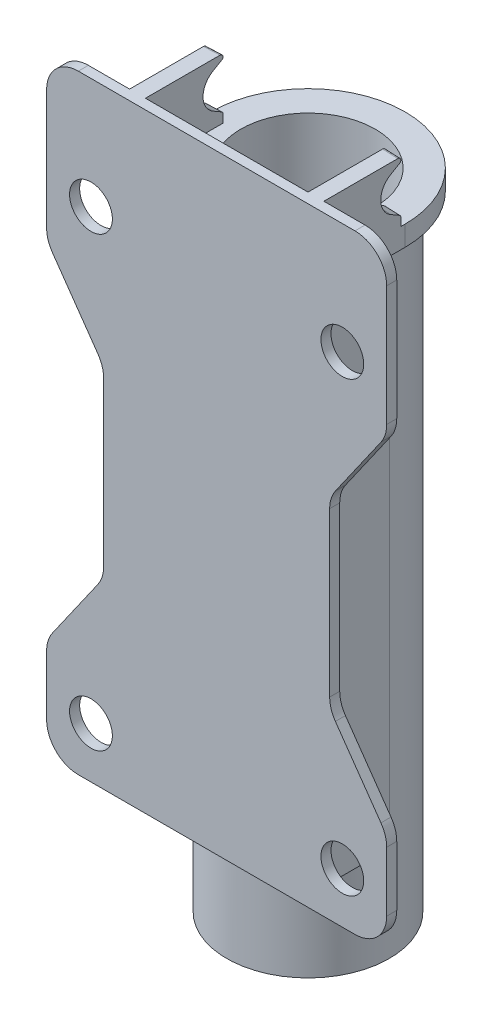
SolidWorks part; units mm, degrees
note: The reader was unsure of these and kept them because the rebuilt part matched: shared geometry of "Sketch33<3>".
other "pipe" parameters "D1"=877.6559, "D2"=75.5022, "D3"=726.6514, "D4"=726.6514, "D5"=877.6559, "D6"=4.445, "D7"=9.9955, "\"bearing_bore_min\""=42.164, "D8"=59.5421, "D9"=6.35, "D10"=1.4503
material "6061 Alloy"
ref_plane "Front Plane" through (0, 0, 0) normal (0, 0, 1) x (1, 0, 0)
ref_plane "Top Plane" through (0, 0, 0) normal (0, 1, 0) x (1, 0, 0)
ref_plane "Right Plane" through (0, 0, 0) normal (1, 0, 0) x (0, 0, -1)
sketch "Sketch11" plane through (0, 0, 0) normal (0, 0, 1) x (1, 0, 0)
  line L0 (0, 0) -> (0, 109.6398) construction
  line L1 (0, 0) -> (-89.1372, 0) construction
sketch "Sketch12" plane through (0, 0, 0) normal (0, 0, 1) x (1, 0, 0)
  line L0 (-25.65, 0) -> (-25.65, 203.2)
  line L1 (200000, 0) -> (-200089.1372, 0) construction
  line L4 (-21.2287, 0) -> (-25.65, 0)
  line L5 (-21.2287, 0) -> (-21.2287, 38.5)
  line L6 (-21.2287, 38.5) -> (-19.177, 38.5)
  line L7 (-19.177, 38.5) -> (-19.177, 164.7)
  line L8 (-19.177, 164.7) -> (-21.2287, 164.7)
  line L9 (-21.2287, 164.7) -> (-21.2287, 203.2)
  line L10 (-21.2287, 203.2) -> (-25.65, 203.2)
  line L13 (-21.2287, 203.2) -> (0, 203.2) construction
  line L14 (0, 203.2) -> (0, 0) construction
  line L15 (0, 0) -> (-21.2287, 0) construction
  point P12 (-25.4, 0)
  dimension "D4" = 38.5
  dimension "D5" = 203.2
  dimension "D6" = 4.4213
  dimension "D1" = 51.3
  dimension "D2" = 42.4573
  dimension "D8" = 50.8
  dimension "D9" = 0.25
  dimension "D3" = 38.354
  dimension "D7" = 2.0517
revolve "Revolve1" add sketch "Sketch12" angle 360 about L0
ref_plane "mideplane" through (0, 101.6, 0) normal (0, -1, 0) x (-1, 0, 0)
ref_plane "top pipe plane" through (0, 30, 0) normal (0, -1, 0) x (-1, 0, 0)
ref_plane "bottom pipe plane" through (0, 203.2, 0) normal (0, 1, 0) x (1, 0, 0)
ref_plane "pipe support midplane" through (0, 116.6, 0) normal (0, -1, 0) x (-1, 0, 0)
sketch "Sketch14" plane through (0, 30, 0) normal (0, -1, 0) x (-1, 0, 0)
  line L0 (0, 0) -> (-25.65, 0) construction
  line L1 (0, 0) -> (25.65, 0) construction
  line L7 (-25.65, -25.65) -> (25.65, -25.65)
  line L9 (25.65, -25.65) -> (25.65, 0)
  line L10 (-25.65, -25.65) -> (-25.65, 0)
  circle A0 centre (0, 0) radius 25.65 construction
  circle A1 centre (0, 0) radius 25.65
  circle A2 centre (0, 0) radius 25.65 construction
  arc A3 (25.65, 0) -> (-25.65, 0) centre (0, 0) cw
  dimension "D1" = 0
  dimension "D2" = 0
extrude "Boss-Extrude1" add sketch "Sketch14" against normal up to surface (173.2 mm away) contours A1 L10 L7 L9 | A1 L7 L9 up to plane "bottom pipe plane"
sketch "Sketch27" plane through (0, 0, 25.65) normal (0, 0, 1) x (1, 0, 0)
  line L0 (25.65, 30) -> (53.65, 30)
  line L1 (53.65, 30) -> (53.65, 62)
  line L2 (53.65, 62) -> (35.65, 87.7067)
  line L3 (35.65, 87.7067) -> (35.65, 145.4933)
  line L4 (35.65, 145.4933) -> (53.65, 171.2)
  line L5 (25.65, 30) -> (25.65, 203.2)
  line L6 (25.65, 203.2) -> (-25.65, 203.2)
  line L7 (-25.65, 203.2) -> (-25.65, 30)
  line L8 (-25.65, 30) -> (0, 30)
  line L9 (0, 30) -> (25.65, 30)
  line L10 (25.65, 30) -> (25.65, 203.2) construction
  line L11 (25.65, 203.2) -> (-25.65, 203.2)
  line L12 (-25.65, 203.2) -> (-25.65, 30)
  line L13 (-25.65, 30) -> (0, 30)
  line L14 (0, 30) -> (25.65, 30)
  line L15 (53.65, 171.2) -> (53.65, 203.2)
  line L16 (25.65, 203.2) -> (53.65, 203.2)
  line L17 (53.65, 62) -> (25.65, 62) construction
  line L18 (25.65, 62) -> (53.65, 30) construction
  line L19 (53.65, 171.2) -> (25.65, 171.2) construction
  line L20 (25.65, 171.2) -> (53.65, 203.2) construction
  line L24 (53.65, 203.2) -> (53.65, 222.25)
  line L25 (53.65, 222.25) -> (-25.65, 222.25)
  line L26 (-25.65, 222.25) -> (-25.65, 203.2)
  circle A0 centre (39.65, 46) radius 6 construction
  point P14 (39.65, 187.2)
  dimension "D2" = 12
  dimension "D3" = 10
  dimension "D6" = 8
  dimension "D4" = 10
  dimension "D5" = 55
  dimension "D7" = 19.05
  dimension "D1" = 0
extrude "Boss-Extrude2" add sketch "Sketch27" along normal blind 3.175
hole_wizard "M12 Clearance Hole1" positions "Sketch28" profile "Sketch29" hole size "M12" standard "ISO" end condition through all
sketch "Sketch28" plane through (0, 0, 25.65) normal (0, 0, -1) x (-1, 0, 0)
  point P0 (-39.65, 46)
  point P3 (-39.65, 187.2)
sketch "Sketch29" plane through (39.65, 46, 25.65) normal (1, 0, 0) x (0, 1, 0)
  line L0 (0, 0) -> (0, 3.175)
  line L1 (0, 3.175) -> (6.75, 3.175)
  line L2 (6.75, 3.175) -> (6.75, 0)
  line L5 (6.75, 0) -> (0, 0)
  line L11 (0, -6.35) -> (0, 107.95) construction
  dimension "Thru Hole Dia." = 13.5
  dimension "Thru Hole Depth" = 3.175
fillet "Fillet1" radius 10 6 edges at (53.65, 171.2, 27.2375) (35.65, 145.4933, 27.2375) (35.65, 87.7067, 27.2375) (53.65, 62, 27.2375) (53.65, 30, 27.2375) (53.65, 222.25, 27.2375)
mirror "Mirror1" about plane through (0, 0, 0) normal (1, 0, 0) of "Fillet1", "M12 Clearance Hole1", "Boss-Extrude2"
chamfer "Chamfer1" [suppressed] distance 1 angle 45
chamfer "Chamfer3" [suppressed] distance 1.85 angle 45
ref_plane "Plane6" through (0, 0, 25.65) normal (0, 0, -1) x (-1, 0, 0)
ref_plane "Plane4" through (0, 203.2, 0) normal (0, 1, 0) x (1, 0, 0)
sketch "Sketch25" plane through (0, 203.2, 0) normal (0, 1, 0) x (1, 0, 0)
  line L0 (-0.277, -6.344) -> (24.5509, -7.428) construction
  line L1 (0.277, 6.344) -> (25.1049, 5.2599) construction
  line L2 (0, 0) -> (25.6256, -1.1188) construction
  line L3 (0, 0) -> (25.6256, -1.1188) construction
  line L4 (35.6186, 0) -> (47.6837, 0) construction
  line L5 (24.5509, -7.428) -> (25.1049, 5.2599) construction
  circle A2 centre (0, 0) radius 25.65 construction
  circle A4 centre (0, 0) radius 6.35 construction
  arc A5 (25.65, 0) -> (-25.65, 0) centre (0, 0) ccw construction
  arc A6 (25.6256, -1.1188) -> (-25.65, 0) centre (0, 0) ccw
  circle A7 centre (0, 0) radius 25.4 construction
  dimension "D3" = 12.7
  dimension "D1" = 50.8
  dimension "D2" = 2.5
ref_plane "Plane5" through (24.8279, 0, 1.084) normal (0.999, 0, 0.0436) x (0.0436, 0, -0.999)
sketch "Sketch26" plane through (24.8279, 0, 1.084) normal (0.999, 0, 0.0436) x (0.0436, 0, -0.999)
  line L0 (-6.35, 203.2) -> (6.35, 203.2) construction
  line L1 (-6.35, 203.2) -> (6.35, 203.2) construction
  line L2 (-6.35, 203.2) -> (-6.35, 226.9306) construction
  circle A0 centre (0, 213.55) radius 6.35
  dimension "D1" = 12.7
  dimension "D2" = 4
sketch "Sketch33" plane through (0, 203.2, 0) normal (0, 1, 0) x (1, 0, 0)
  line L0 (30.65, -25.65) -> (30.65, 0)
  line L1 (-30.65, 0) -> (-30.65, -25.65)
  line L2 (-30.65, -25.65) -> (-25.65, -25.65)
  line L3 (-25.65, 0) -> (-25.65, -25.65)
  line L4 (-25.65, -25.65) -> (25.65, -25.65)
  line L5 (25.65, -25.65) -> (25.65, 0)
  line L6 (-25.65, 0) -> (-25.65, -25.65)
  line L7 (-25.65, -25.65) -> (25.65, -25.65)
  line L8 (25.65, -25.65) -> (25.65, 0)
  line L9 (25.65, -25.65) -> (30.65, -25.65)
  line L10 (0, 0) -> (25.6256, -1.1188) construction
  line L11 (0, 0) -> (25.6256, -1.1188) construction
  line L12 (25.6256, -1.1188) -> (30.65, -1.3382)
  arc A0 (30.65, 0) -> (-30.65, 0) centre (0, 0) ccw
  arc A1 (25.65, 0) -> (-25.65, 0) centre (0, 0) ccw
  arc A2 (25.65, 0) -> (-25.65, 0) centre (0, 0) ccw
  point P12 (30.65, -1.3382)
  arc M5 (25.65, 0) -> (-25.65, 0) centre (0, 0) ccw
  line M6 (-25.65, 0) -> (-25.65, -25.65)
  line M8 (25.65, -25.65) -> (25.65, 0)
  dimension "D1" = 0
  dimension "D2" = 5
extrude "Boss-Extrude3" add sketch "Sketch33" against normal blind 6.35 contours L0 A0 L1 L2 L9 M6 M5 M8 | L12 L9 L0 M8
extrude "Boss-Extrude4" add sketch "Sketch33<3>" along normal blind 19.05 contours L12 L9 L0 M8 | L8 A2 L6
sketch "Sketch33<3>" plane through (0, 203.2, 0) normal (0, 1, 0) x (1, 0, 0) same geometry as "Sketch33"
sketch "Sketch34" plane through (24.8279, 0, 1.084) normal (0.999, 0, 0.0436) x (0.0436, 0, -0.999)
  line L0 (-3.175, 219.0493) -> (0, 220.8823)
  line L1 (0, 213.55) -> (-3.175, 219.0493)
  line L2 (0, 213.55) -> (0, 219.9) construction
  line L3 (0, 213.55) -> (0, 207.2) construction
  line L4 (0, 213.55) -> (-3.175, 208.0507)
  line L5 (-3.175, 208.0507) -> (0, 206.2177)
  line L6 (0, 222.25) -> (0, 203.2) construction
  line L7 (0, 222.25) -> (0, 203.2)
  circle A0 centre (0, 213.55) radius 6.35 construction
  circle A1 centre (0, 213.55) radius 6.35
  point P11 (0, 0)
  point P12 (0, 0)
  point P13 (0, 221.2339)
  dimension "D1" = 30
  dimension "D2" = 30
extrude "Cut-Extrude1" cut sketch "Sketch34" against normal through all both and the other way through all contours L7 A1 L1 | L1 A1 L4 | A1 L7 L0 | L4 A1 L7 | A1 L5 L7
fillet "Fillet2" radius 1 3 edges at (28.15, 220.8823, 1.2291) (28.15, 222.25, 1.2291) (28.15, 206.2177, 1.2291)
mirror "Mirror2" about plane through (0, 0, 0) normal (1, 0, 0) of "Fillet2", "Cut-Extrude1", "Boss-Extrude4"
equation "\"bearing_bore\"= 1 + 21 / 32in"
equation "\"bearing_bore_max\"= 1.6568in"
equation "\"bearing_bore_min\"= 1.6558in"
equation "\"shaft_dia\"= 1.5in"
equation "\"shaft_dia_min\"= 1.51in"
equation "\"D2@Sketch12\"=\"bearing_bore_min\"+0.4mm"
equation "\"bearing_flange_diameter\"= 2in"
equation "\"bearing_flange_thickness\"= 0.078in"
equation "\"bearing_length\"= 1.5in"
equation "\"D8@Sketch12\"=\"bearing_flange_diameter\""
equation "\"D4@Sketch12\"=\"bearing_length\"+0.4"
equation "\"D1@Sketch25\"=\"bearing_flange_diameter\""
equation "\"nub_dia\"= 0.5in"
equation "\"D1@Sketch26\"=\"nub_dia\""
equation "\"D1@Sketch31\"=\"bearing_flange_diameter\""
equation "\"D1@Sketch12\"=\"bearing_flange_diameter\"+0.5"
